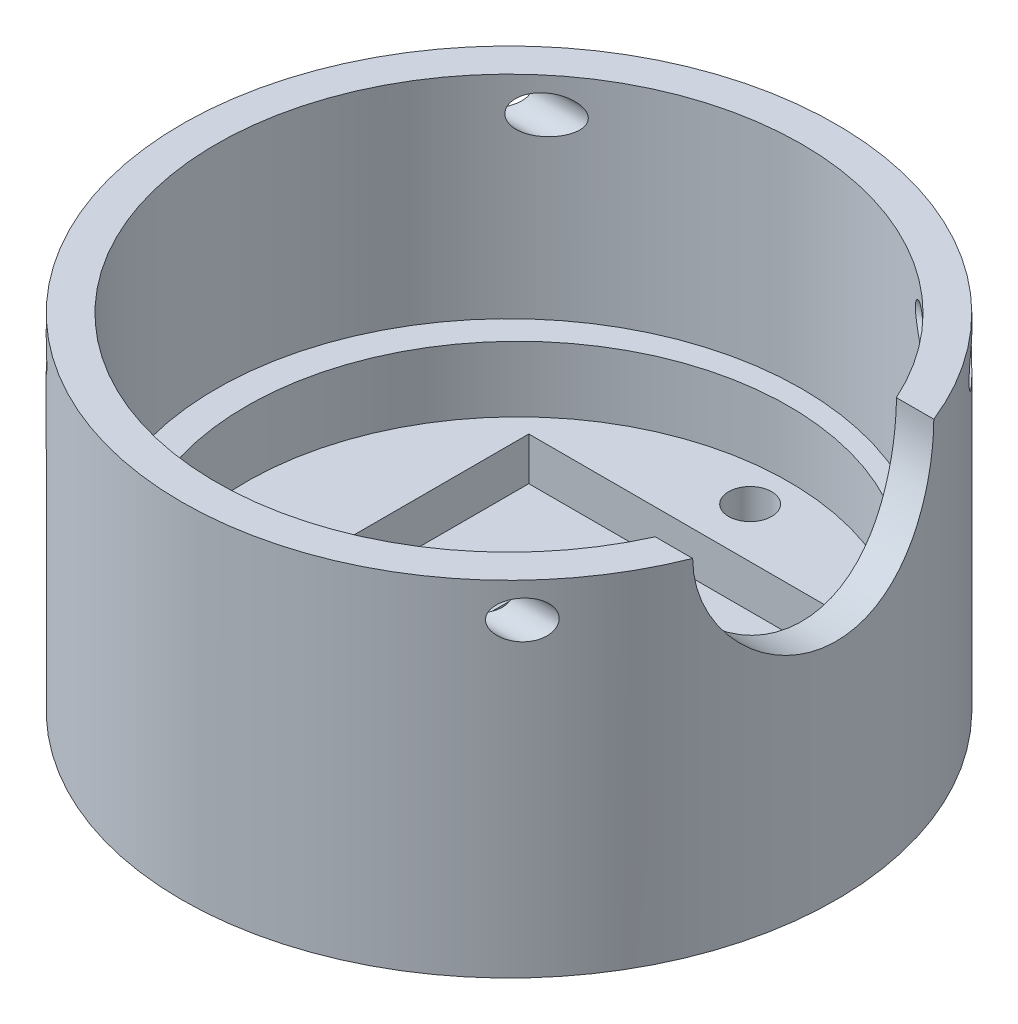
SolidWorks part; units mm, degrees
ref_plane "Front Plane" through (0, 0, 0) normal (0, 0, 1) x (1, 0, 0)
ref_plane "Top Plane" through (0, 0, 0) normal (0, 1, 0) x (1, 0, 0)
ref_plane "Right Plane" through (0, 0, 0) normal (1, 0, 0) x (0, 0, -1)
sketch "Sketch3" plane through (0, 0, 0) normal (0, 1, 0) x (1, 0, 0)
  circle A0 centre (0, 0) radius 19
  dimension "D1" = 38
extrude "Main Body" add sketch "Sketch3" against normal blind 20
sketch "Sketch5" plane through (0, -20, 0) normal (0, -1, 0) x (1, 0, 0)
  circle A0 centre (0, 0) radius 17
  circle A1 centre (0, 0) radius 19 construction
  dimension "D1" = 2
extrude "Cut for Headers" cut sketch "Sketch5" against normal through all from offset 7.7 offset against normal yes
ref_axis "Central Axis" through (0, 1, 0) along (0, -1, 0)
ref_axis "Horizontal Axis" through (-20.9, 0, 0) along (1, 0, 0)
ref_axis "Vertical Axis" through (0, 0, -20.9) along (0, 0, 1)
sketch "Sketch7" plane through (0, 0, 0) normal (1, 0, 0) x (0, 0, -1)
  circle A0 centre (0, 0) radius 7
  point P3 (0, -3.3432)
  dimension "D1" = 14
extrude "Cut for ADNS Wires" cut sketch "Sketch7" along normal up to next
sketch "Sketch8" plane through (0, -12.3, 0) normal (0, 1, 0) x (1, 0, 0)
  circle A0 centre (0.5, 0) radius 15.75
  dimension "D1" = 31.5
  dimension "D2" = 0.5
extrude "Cut for PCB" cut sketch "Sketch8" against normal blind 3.8
sketch "Sketch9" plane through (0, -16.1, 0) normal (0, 1, 0) x (1, 0, 0)
  line L0 (0.5, 15.75) -> (0.5, -15.75) construction
  line L1 (-15.25, 0) -> (16.25, 0) construction
  circle A1 centre (0.5, 0) radius 15.75 construction
  circle A2 centre (0.5, 13.5) radius 1.25
  circle A3 centre (0.5, -13.5) radius 1.25
  point P0 (0, 0)
  dimension "D1" = 2.5
  dimension "D2" = 27
extrude "Cut for Screw Holes" cut sketch "Sketch9" against normal blind 5
sketch "Sketch10" plane through (0, -16.1, 0) normal (0, 1, 0) x (1, 0, 0)
  line L1 (-9.45, -10.6) -> (9.45, -10.6)
  line L2 (-9.45, -10.6) -> (-9.45, 10.6)
  line L3 (-9.45, 10.6) -> (9.45, 10.6)
  line L4 (9.45, -10.6) -> (9.45, 10.6)
  line L5 (-9.45, -10.6) -> (9.45, 10.6) construction
  line L6 (-9.45, 10.6) -> (9.45, -10.6) construction
  point P0 (0, 0)
  dimension "D1" = 18.9
  dimension "D2" = 21.2
extrude "Cut for Lens" cut sketch "Sketch10" against normal blind 2.5
sketch "Sketch11" plane through (0, -18.6, 0) normal (0, 1, 0) x (1, 0, 0)
  line L1 (-4.1, -5.1) -> (4.1, -5.1)
  line L2 (-4.1, -5.1) -> (-4.1, 5.1)
  line L3 (-4.1, 5.1) -> (4.1, 5.1)
  line L4 (4.1, -5.1) -> (4.1, 5.1)
  line L5 (-4.1, -5.1) -> (4.1, 5.1) construction
  line L6 (-4.1, 5.1) -> (4.1, -5.1) construction
  point P0 (0, 0)
  dimension "D1" = 10.2
  dimension "D2" = 8.2
extrude "Cut for Pupil" cut sketch "Sketch11" against normal up to next
sketch "Sketch13" plane through (0, 0, 0) normal (1, 0, 0) x (0, 0, -1)
  line L0 (0, 1) -> (0, -21) construction
  line L1 (20.9, 0) -> (-20.9, 0) construction
  circle A0 centre (13, -2) radius 1.1
  circle A1 centre (-13, -2) radius 1.1
  point P0 (13, -2)
  point P7 (-13, -2)
  dimension "D3" = 2.2
  dimension "D4" = 13
  dimension "D5" = 2.2
  dimension "D1" = 13
  dimension "D2" = 2
extrude "Cuts for Body Screw Holes" cut sketch "Sketch13" against normal through all both and the other way through all
